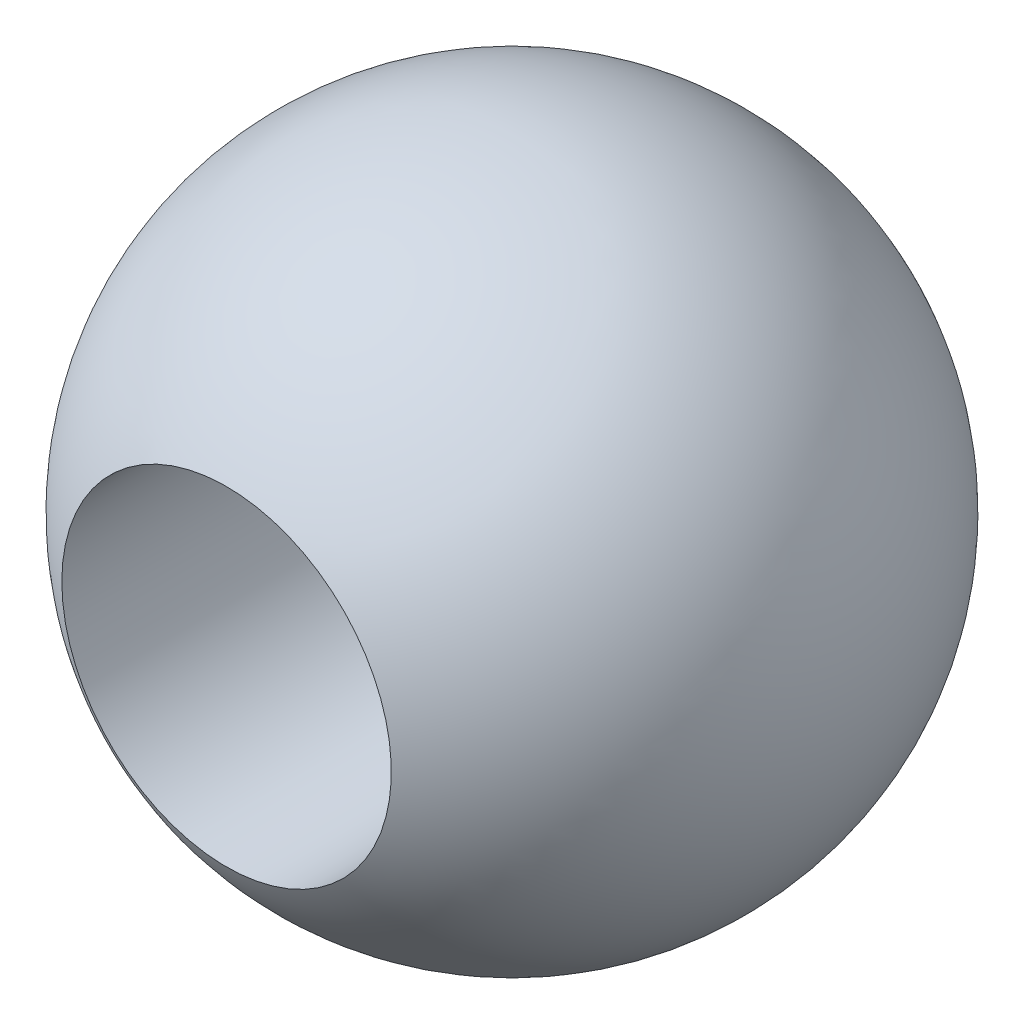
SolidWorks part; units mm, degrees
ref_plane "Front Plane" through (0, 0, 0) normal (0, 0, 1) x (1, 0, 0)
ref_plane "Top Plane" through (0, 0, 0) normal (0, 1, 0) x (1, 0, 0)
ref_plane "Right Plane" through (0, 0, 0) normal (1, 0, 0) x (0, 0, -1)
sketch "Sketch1" plane through (0, 0, 0) normal (0, 0, 1) x (1, 0, 0)
  line L1 (0, -59.5999) -> (0, 2920.3972) construction
  arc A0 (0, 3.175) -> (0, -3.175) centre (0, 0) ccw
  circle A1 centre (0, 0) radius 1.5875
  dimension "D1" = 3.175
  dimension "D2" = 3.175
revolve "Revolve1" add sketch "Sketch1" angle 360 about L1 region at (-3.104, 0, 0)
extrude "Cut-Extrude1" cut sketch "Sketch1<3>" against normal through all both and the other way through all contours A1
sketch "Sketch1<3>" plane through (0, 0, 0) normal (0, 0, 1) x (1, 0, 0) same geometry as "Sketch1"
